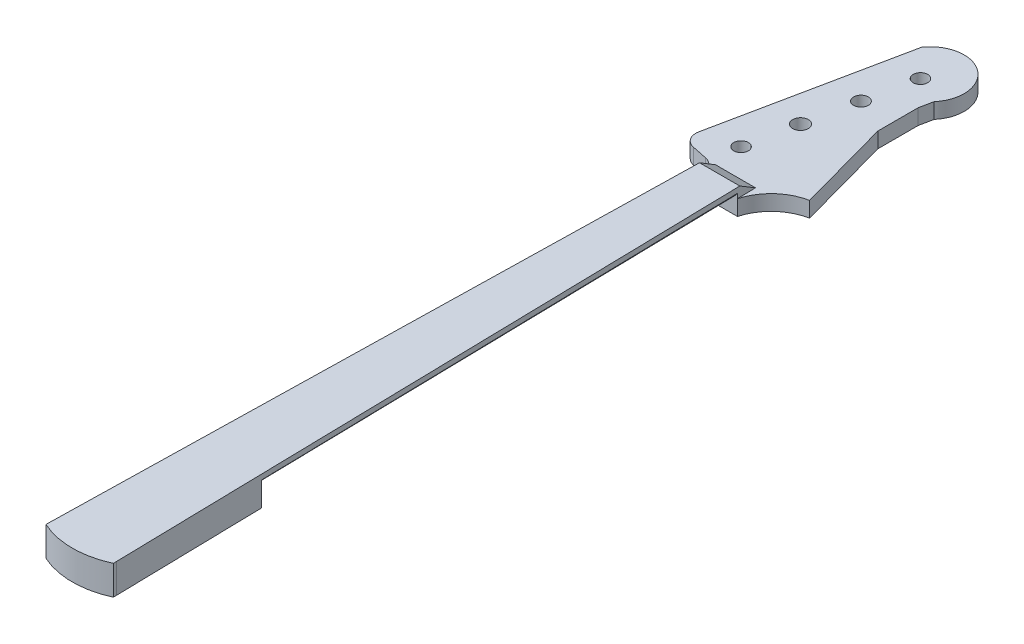
SolidWorks part; units mm, degrees
ref_plane "Front Plane" through (0, 0, 0) normal (0, 0, 1) x (1, 0, 0)
ref_plane "Top Plane" through (0, 0, 0) normal (0, 1, 0) x (1, 0, 0)
ref_plane "Right Plane" through (0, 0, 0) normal (1, 0, 0) x (0, 0, -1)
sketch "Sketch1" plane through (0, 0, 0) normal (0, 0, 1) x (1, 0, 0)
  line L0 (-19.05, 0) -> (19.05, 0)
  line L1 (19.05, 0) -> (19.05, -4.826)
  line L2 (19.05, -4.826) -> (-19.05, -4.826)
  line L3 (-19.05, -4.826) -> (-19.05, 0)
  point P6 (0, 0)
  dimension "D1" = 38.1
  dimension "D2" = 4.826
ref_plane "Plane1" through (0, 0, 598.4875) normal (0, 0, 1) x (1, 0, 0)
sketch "Sketch2" plane through (0, 0, 598.4875) normal (0, 0, 1) x (1, 0, 0)
  line L0 (19.05, -4.826) -> (-19.05, -4.826) construction
  line L1 (-31.75, 0) -> (31.75, 0)
  line L2 (-31.75, 0) -> (-31.75, -4.826)
  line L3 (-31.75, -4.826) -> (31.75, -4.826)
  line L4 (31.75, 0) -> (31.75, -4.826)
  line L5 (-19.05, 0) -> (19.05, 0) construction
  point P8 (0, 0)
  dimension "D1" = 63.5
loft "Loft1" add profiles "Sketch1", "Sketch2" connector at (-19.05, 0, 0) connector at (-31.75, 0, 598.4875)
sketch "Sketch3" plane through (0, 0, 0) normal (0, 0, -1) x (-1, 0, 0)
  line L0 (19.05, -4.826) -> (-19.05, -4.826) construction
  line L1 (19.05, -4.826) -> (-19.05, -4.826)
  arc A0 (-19.05, -4.826) -> (19.05, -4.826) centre (0, 7.5791) ccw
  dimension "D1" = 22.733
ref_plane "Plane2" through (0, 0, 458.7875) normal (0, 0, 1) x (1, 0, 0)
sketch "Sketch5" plane through (0, -4.826, 0) normal (0, -1, 0) x (1, 0, 0)
  line L0 (19.05, 0) -> (31.75, 598.4875) construction
  line L1 (28.7855, 458.7875) -> (31.75, 598.4875)
  line L2 (-19.05, 0) -> (-31.75, 598.4875) construction
  line L3 (-28.7855, 458.7875) -> (-31.75, 598.4875)
  line L4 (-31.75, 598.4875) -> (31.75, 598.4875)
  line L5 (-28.7855, 458.7875) -> (28.7855, 458.7875)
  line L6 (13.6811, 458.7875) -> (-13.6811, 458.7875) construction
extrude "Boss-Extrude1" add sketch "Sketch5" along normal blind 22.86
sketch "Sketch4" plane through (0, 0, 458.7875) normal (0, 0, 1) x (1, 0, 0)
  line L3 (-28.7855, -4.826) -> (28.7855, -4.826)
  line L4 (-19.05, -4.826) -> (19.05, -4.826) construction
  line L5 (-28.7855, -4.826) -> (28.7855, -4.826) construction
  arc A1 (-28.7855, -4.826) -> (28.7855, -4.826) centre (0, 18.034) ccw
  point P6 (0, -4.826)
  point P9 (0, -4.826)
  dimension "D1" = 22.86
loft "Loft2" add profiles "Sketch4", "Sketch3" connector at (-28.7855, -4.826, 458.7875) connector at (-19.05, -4.826, 0)
sketch "Sketch6" plane through (0, 0, 0) normal (0, 1, 0) x (1, 0, 0)
  line L0 (-31.75, -598.4875) -> (-31.75, -601.5355)
  line L2 (31.75, -598.4875) -> (31.75, -601.5355)
  line L5 (31.75, -598.4875) -> (-31.75, -598.4875) construction
  line L6 (31.75, -598.4875) -> (-31.75, -598.4875)
  arc A0 (-31.75, -601.5355) -> (31.75, -601.5355) centre (0, -532.8689) ccw
  point P2 (0, -608.5205)
  dimension "D1" = 6.985
  dimension "D2" = 3.048
extrude "Boss-Extrude2" add sketch "Sketch6" against normal up to surface (27.686 mm away) up to face at (0, -27.686, 528.6375)
ref_plane "Plane3" through (0, -23.749, 0) normal (0, 1, 0) x (1, 0, 0)
sketch "Sketch7" plane through (0, -23.749, 0) normal (0, 1, 0) x (1, 0, 0)
  line L0 (-53.7966, 36.3949) -> (-17.8583, 210.525)
  line L1 (-43.9257, 21.39) -> (-29.183, 18.3473)
  line L2 (32.5646, 172.0943) -> (29.9976, 159.6564)
  line L3 (-19.05, 0) -> (19.05, 0)
  line L4 (19.05, 0) -> (19.1268, -3.6195) construction
  line L5 (19.05, 0) -> (31.75, -598.4875) construction
  line L6 (19.1268, -3.6195) -> (-19.1268, -3.6195) construction
  line L7 (-19.05, 0) -> (-31.75, -598.4875) construction
  line L8 (-19.1268, -3.6195) -> (-19.05, 0) construction
  line L9 (-14.859, 0) -> (-14.859, -3.6195) construction
  line L10 (-4.7244, 0) -> (-4.7244, -3.6195) construction
  line L11 (4.572, 0) -> (4.572, -3.6195) construction
  line L12 (14.097, 0) -> (14.097, -3.6195) construction
  line L13 (-14.859, 0) -> (-14.859, 44.196) construction
  line L14 (-4.7244, 0) -> (-4.7244, 90.7136) construction
  line L15 (4.572, 0) -> (4.572, 137.9775) construction
  line L16 (14.097, 0) -> (14.097, 184.4951) construction
  line L17 (-21.7234, 44.196) -> (7.2326, 184.4951) construction
  line L18 (-19.05, 5.9095) -> (-19.05, 0)
  line L19 (29.9976, 159.6564) -> (29.9976, 121.5564)
  line L20 (29.9976, 121.5564) -> (54.4767, 32.6564)
  arc A1 (32.5646, 172.0943) -> (-17.8583, 210.525) centre (8.4403, 192.7361) ccw
  circle A2 centre (-21.7234, 44.196) radius 6.8643
  circle A3 centre (-12.1227, 90.7136) radius 7.3983
  circle A4 centre (-2.368, 137.9775) radius 6.94
  circle A5 centre (7.2326, 184.4951) radius 6.8643
  arc A7 (19.05, 0) -> (54.4767, 32.6564) centre (63.1003, -12.2429) cw
  arc A8 (-29.183, 18.3473) -> (-19.05, 5.9095) centre (-31.75, 5.9095) cw
  arc A9 (-53.7966, 36.3949) -> (-43.9257, 21.39) centre (-41.3587, 33.8279) ccw
  point P45 (-19.05, 16.256)
  point P48 (-56.3636, 23.9571)
  dimension "D4" = 13.7287
  dimension "D14" = 14.7966
  dimension "D16" = 63.5
  dimension "D19" = 45.72
  dimension "D20" = 12.7
  dimension "D1" = 190.5
  dimension "D2" = 38.1
  dimension "D3" = 57.15
  dimension "D5" = 3.6195
  dimension "D6" = 4.191
  dimension "D7" = 10.1346
  dimension "D8" = 19.431
  dimension "D9" = 28.956
  dimension "D10" = 47.498
  dimension "D11" = 95.758
  dimension "D12" = 143.256
  dimension "D13" = 44.196
  dimension "D15" = 16.256
  dimension "D17" = 12.7
  dimension "D18" = 76.2
  dimension "D21" = 88.9
  dimension "D22" = 38.1
  dimension "D23" = 172.0943
  dimension "D24" = 164.605
extrude "Boss-Extrude3" add sketch "Sketch7" along normal blind 14.5542
sketch "Sketch8" plane through (-19.05, 0, 0) normal (-1, 0, 0) x (0, 0, 1)
  line L0 (0, 0) -> (-2.286, 0)
  line L1 (-2.286, 0) -> (-17.399, -9.1948)
  line L3 (-5.9095, -9.1948) -> (-18.3473, -9.1948) construction
  line L4 (-17.399, -9.1948) -> (0, -9.1948)
  line L5 (0, -9.1948) -> (0, 0)
  dimension "D1" = 2.286
  dimension "D2" = 17.399
extrude "Boss-Extrude4" add sketch "Sketch8" against normal up to surface (37.7308 mm away) up to face at (25.6719, -13.9337, 312.0571)
sketch "Sketch9" plane through (0, -27.686, 0) normal (0, -1, 0) x (1, 0, 0)
  line L0 (28.7855, 458.7875) -> (31.75, 598.4875) construction
  line L1 (18.9681, 572.2902) -> (18.9681, 606.104) construction
  line L2 (-31.75, 598.4875) -> (-28.7855, 458.7875) construction
  circle A0 centre (-18.4599, 572.2902) radius 2.0637
  circle A1 centre (18.9681, 572.2902) radius 2.0637
  circle A2 centre (19.0266, 521.1727) radius 2.0637
  circle A3 centre (-18.1374, 521.1727) radius 2.0637
  arc A4 (31.75, 601.5355) -> (-31.75, 601.5355) centre (0, 532.8689) ccw construction
  point P8 (21.0318, 572.2902)
  point P11 (18.9681, 570.2265)
  point P12 (19.0266, 523.2365)
  point P13 (21.0903, 521.1727)
  point P14 (18.9681, 574.354)
  point P20 (-20.5237, 572.2902)
  point P22 (-20.2011, 521.1727)
  point P23 (0, 0)
  dimension "D1" = 4.1275
  dimension "D2" = 10.16
  dimension "D3" = 46.99
  dimension "D4" = 9.017
  dimension "D5" = 31.75
  dimension "D6" = 10.668
  dimension "D7" = 9.906
extrude "Cut-Extrude1" cut sketch "Sketch9" against normal blind 10.16
